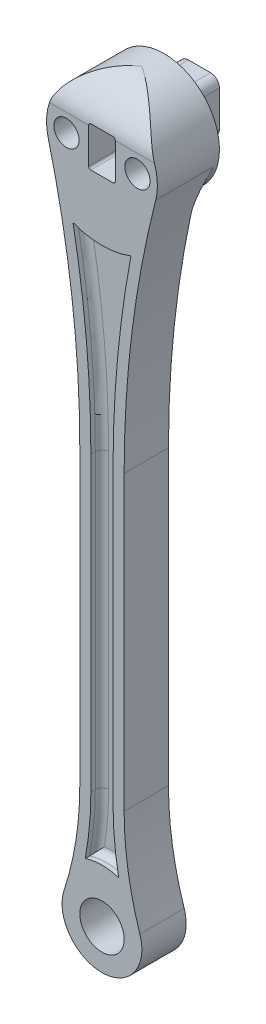
SolidWorks part; units mm, degrees
ref_plane "Front Plane" through (0, 0, 0) normal (0, 0, 1) x (1, 0, 0)
ref_plane "Top Plane" through (0, 0, 0) normal (0, 1, 0) x (1, 0, 0)
ref_plane "Right Plane" through (0, 0, 0) normal (1, 0, 0) x (0, 0, -1)
sketch "Sketch1" plane through (0, 0, 0) normal (0, 0, 1) x (1, 0, 0)
  line L0 (0, 0) -> (0, 6) construction
  line L1 (-4.5, -6) -> (4.5, -6) construction
  line L2 (-4.5, -6) -> (-4.5, 6) construction
  line L3 (-4.5, 6) -> (4.5, 6) construction
  line L4 (4.5, -6) -> (4.5, 6) construction
  line L5 (-4.5, -6) -> (4.5, 6) construction
  line L6 (-4.5, 6) -> (4.5, -6) construction
  circle A0 centre (8, 0) radius 1.65
  circle A1 centre (-8, 0) radius 1.65
  circle A2 centre (0, 0) radius 12.5
  point P0 (0, 0)
  dimension "D3" = 3.3
  dimension "D5" = 25
  dimension "D1" = 9
  dimension "D2" = 12
  dimension "D4" = 8
extrude "Boss-Extrude1" add sketch "Sketch1" along normal blind 4
sketch "Sketch2" plane through (0, 0, 0) normal (0, 0, -1) x (-1, 0, 0)
  line L0 (-4.5, -6) -> (-4.5, 6) construction
  line L1 (4.5, -6) -> (-4.5, -6) construction
  line L2 (4.5, -6) -> (4.5, 6) construction
  line L3 (4.5, 6) -> (-4.5, 6) construction
  line L4 (-4.5, -6) -> (-4.5, 6)
  line L5 (4.5, -6) -> (-4.5, -6)
  line L6 (4.5, -6) -> (4.5, 6)
  line L7 (4.5, 6) -> (-4.5, 6)
extrude "Boss-Extrude2" add sketch "Sketch2" along normal blind 8
fillet "Fillet1" radius 2 4 edges at (-4.5, 6, -4) (4.5, 6, -4) (4.5, -6, -4) (-4.5, -6, -4)
sketch "Sketch3" plane through (0, 0, 4) normal (0, 0, 1) x (1, 0, 0)
  line L0 (0, 0) -> (0, -160) construction
  line L1 (5, -60) -> (5, -126)
  line L2 (-5, -60) -> (-5, -126)
  arc A0 (-8.5507, -148.1919) -> (8.5507, -148.1919) centre (0, -151) ccw
  circle A1 centre (0, -151) radius 5
  arc A2 (5, -126) -> (8.5507, -148.1919) centre (76.125, -126) ccw
  circle A3 centre (0, 0) radius 12.5 construction
  arc A4 (12.1154, -3.0769) -> (-12.1154, -3.0769) centre (0, 0) ccw
  arc A5 (5, -60) -> (12.1154, -3.0769) centre (236.25, -60) cw
  arc A6 (-5, -126) -> (-8.5507, -148.1919) centre (-76.125, -126) cw
  arc A7 (-5, -60) -> (-12.1154, -3.0769) centre (-236.25, -60) ccw
  circle A8 centre (8, 0) radius 1.65 construction
  circle A9 centre (-8, 0) radius 1.65 construction
  circle A10 centre (8, 0) radius 1.65
  circle A11 centre (-8, 0) radius 1.65
  dimension "D2" = 18
  dimension "D3" = 10
  dimension "D1" = 160
  dimension "D4" = 5
  dimension "D5" = 25
  dimension "D6" = 60
extrude "Boss-Extrude3" add sketch "Sketch3" along normal blind 10
fillet "Fillet2" radius 3 1 edges at (0, -12.5, 4)
sketch "Sketch5" plane through (0, 0, 0) normal (1, 0, 0) x (0, 0, -1)
  line L0 (-5, 12.5) -> (-9, 12.5) construction
  line L3 (-9, 12.5) -> (-14, 8) construction
  line L5 (-14, 8) -> (-14, 4) construction
  line L6 (0, 12.5) -> (-14, 12.5) construction
  line L7 (0, -12.5) -> (0, 12.5) construction
  line L8 (-14, 12.5) -> (-14, -3.0769) construction
  line L9 (-5, 12.5) -> (-8.5928, 18.197)
  line L10 (-8.5928, 18.197) -> (-19.9497, 14.0098)
  line L11 (-19.9497, 14.0098) -> (-14, 4)
  spline S0 degree 3 poles (-5, 12.5) (-9, 12.5) (-14, 8) (-14, 4) knots 0 0 0 0 1 1 1 1
  dimension "D1" = 5
  dimension "D2" = 4
  dimension "D3" = 4
  dimension "D4" = 4
extrude "Cut-Extrude2" cut sketch "Sketch5" against normal mid plane 38
sketch "Sketch4" plane through (0, 0, 14) normal (0, 0, 1) x (1, 0, 0)
  circle A0 centre (-8, 0) radius 1.65 construction
  circle A1 centre (8, 0) radius 1.65 construction
  circle A2 centre (-8, 0) radius 1.65 construction
  circle A3 centre (8, 0) radius 1.65 construction
  circle A4 centre (8, 0) radius 2.85
  circle A5 centre (-8, 0) radius 2.85
  dimension "D1" = 5.7
  dimension "D2" = 5.7
extrude "Cut-Extrude1" cut sketch "Sketch4" against normal blind 9
sketch "Sketch6" plane through (0, 0, 14) normal (0, 0, 1) x (1, 0, 0)
  line L6 (0, -18) -> (0, -151) construction
  line L7 (-2.5, -126) -> (-2.5, -60)
  line L8 (-2.5, -126) -> (-2.5, -60)
  line L9 (2.5, -126) -> (2.5, -60)
  arc A4 (-6.5317, -16.7731) -> (6.5317, -16.7731) centre (0, 0) ccw
  arc A5 (3.7683, -139.607) -> (-3.7683, -139.607) centre (0, -151) ccw
  arc A6 (-6.1755, -148.9719) -> (-2.5, -126) centre (-76.125, -126) ccw
  arc A7 (-2.5, -60) -> (-9.6923, -2.4615) centre (-236.25, -60) ccw
  arc A8 (-3.7683, -139.607) -> (-2.5, -126) centre (-76.125, -126) ccw
  arc A9 (-2.5, -60) -> (-6.5317, -16.7731) centre (-236.25, -60) ccw
  arc A10 (3.7683, -139.607) -> (2.5, -126) centre (76.125, -126) cw
  arc A11 (2.5, -60) -> (6.5317, -16.7731) centre (236.25, -60) cw
  dimension "D2" = 36
  dimension "D3" = 24
  dimension "D1" = 2.5
extrude "Cut-Extrude3" cut sketch "Sketch6" against normal blind 2.5
fillet "Fillet3" radius 1.5 8 edges at (-2.8178, -132.833, 11.5) (-2.5, -93, 11.5) (2.8178, -132.833, 11.5) (2.5, -93, 11.5) (0, -139, 11.5) (-3.5101, -38.2927, 11.5) (0, -18, 11.5) (3.5101, -38.2927, 11.5)
ref_plane "Plane1" through (0, 0, 9) normal (0, 0, 1) x (1, 0, 0)
mirror "Mirror1" about plane through (0, 0, 9) normal (0, 0, 1) of "Fillet3", "Cut-Extrude3"
sketch "Sketch8" plane through (0, 0, -8) normal (0, 0, -1) x (-1, 0, 0)
  line L0 (3, -4) -> (3, 4)
  line L1 (2.5, 4.5) -> (-2.5, 4.5)
  line L2 (-3, 4) -> (-3, -4)
  line L3 (-2.5, -4.5) -> (2.5, -4.5)
  line L4 (4.5, -4) -> (4.5, 4)
  line L5 (2.5, 6) -> (-2.5, 6)
  line L6 (-4.5, 4) -> (-4.5, -4)
  line L7 (-2.5, -6) -> (2.5, -6)
  line L8 (4.5, -4) -> (4.5, 4) construction
  line L9 (2.5, 6) -> (-2.5, 6) construction
  line L10 (-4.5, 4) -> (-4.5, -4) construction
  line L11 (-2.5, -6) -> (2.5, -6) construction
  arc A0 (3, 4) -> (2.5, 4.5) centre (2.5, 4) ccw
  arc A1 (-2.5, 4.5) -> (-3, 4) centre (-2.5, 4) ccw
  arc A2 (-3, -4) -> (-2.5, -4.5) centre (-2.5, -4) ccw
  arc A3 (2.5, -4.5) -> (3, -4) centre (2.5, -4) ccw
  arc A4 (4.5, 4) -> (2.5, 6) centre (2.5, 4) ccw
  arc A5 (-2.5, 6) -> (-4.5, 4) centre (-2.5, 4) ccw
  arc A6 (-4.5, -4) -> (-2.5, -6) centre (-2.5, -4) ccw
  arc A7 (2.5, -6) -> (4.5, -4) centre (2.5, -4) ccw
  arc A8 (4.5, 4) -> (2.5, 6) centre (2.5, 4) ccw construction
  arc A9 (-2.5, 6) -> (-4.5, 4) centre (-2.5, 4) ccw construction
  arc A10 (-4.5, -4) -> (-2.5, -6) centre (-2.5, -4) ccw construction
  arc A11 (2.5, -6) -> (4.5, -4) centre (2.5, -4) ccw construction
  dimension "D1" = 0
  dimension "D2" = 1.5
extrude "Cut-Extrude4" cut sketch "Sketch8" against normal through all
